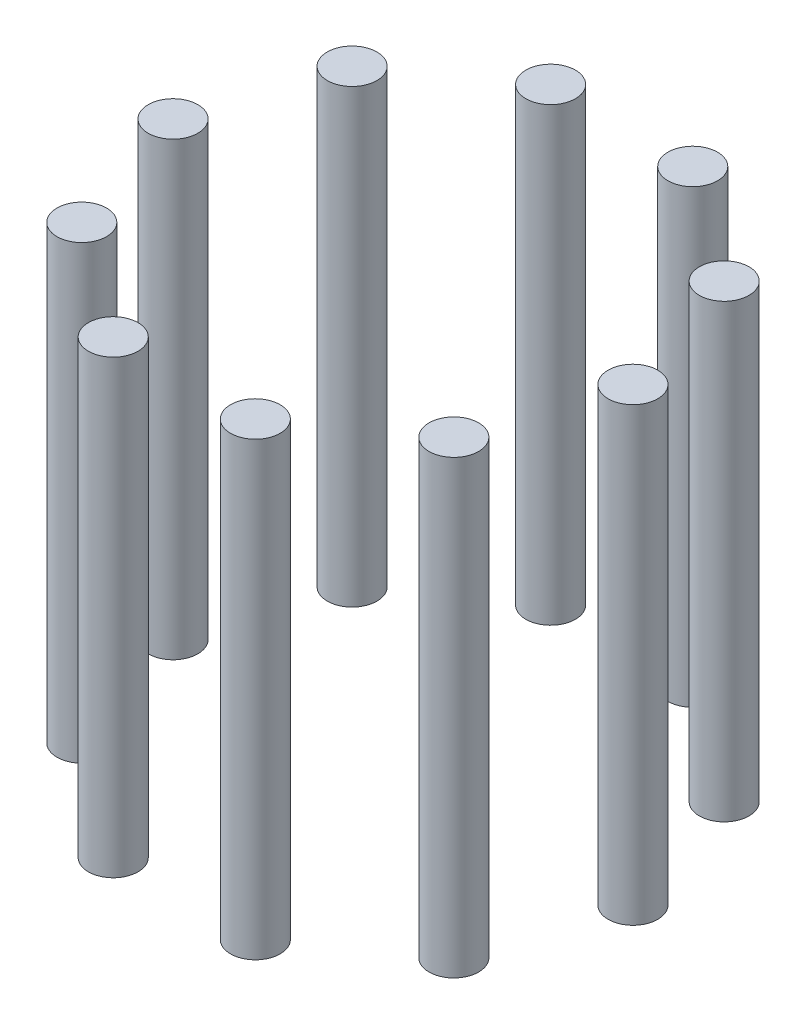
SolidWorks part; units mm, degrees
ref_plane "Front Plane" through (0, 0, 0) normal (0, 0, 1) x (1, 0, 0)
ref_plane "Top Plane" through (0, 0, 0) normal (0, 1, 0) x (1, 0, 0)
ref_plane "Right Plane" through (0, 0, 0) normal (1, 0, 0) x (0, 0, -1)
sketch "Sketch1" plane through (0, 0, 0) normal (0, 1, 0) x (1, 0, 0)
  circle A1 centre (51, 0) radius 5.5
  circle A2 centre (41.2599, -29.977) radius 5.5
  circle A3 centre (15.7599, -48.5039) radius 5.5
  circle A4 centre (-15.7599, -48.5039) radius 5.5
  circle A5 centre (-41.2599, -29.977) radius 5.5
  circle A6 centre (-51, 0) radius 5.5
  circle A7 centre (-41.2599, 29.977) radius 5.5
  circle A8 centre (-15.7599, 48.5039) radius 5.5
  circle A9 centre (15.7599, 48.5039) radius 5.5
  circle A10 centre (41.2599, 29.977) radius 5.5
  point P25 (0, 0)
  dimension "D1" = 10
extrude "Boss-Extrude1" add sketch "Sketch1" along normal blind 100
